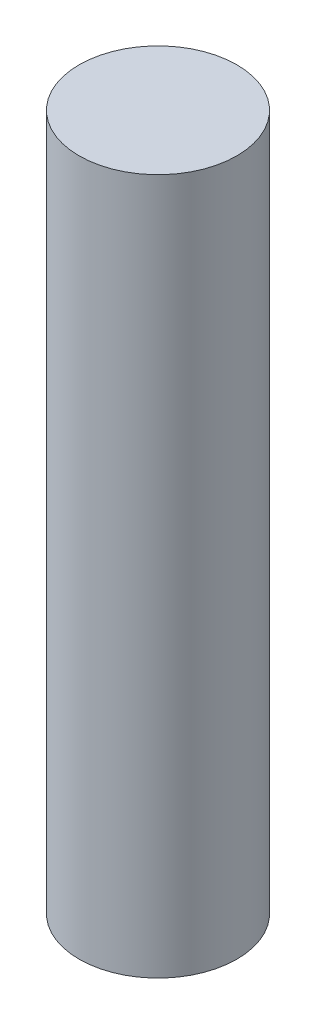
SolidWorks part; units mm, degrees
material "Alloy Steel"
ref_plane "Front Plane" through (0, 0, 0) normal (0, 0, 1) x (1, 0, 0)
ref_plane "Top Plane" through (0, 0, 0) normal (0, 1, 0) x (1, 0, 0)
ref_plane "Right Plane" through (0, 0, 0) normal (1, 0, 0) x (0, 0, -1)
sketch "Sketch1" plane through (0, 0, 0) normal (0, 1, 0) x (1, 0, 0)
  circle A0 centre (0, 0) radius 3.9688
  dimension "D1" = 7.9375
extrude "Boss-Extrude1" add sketch "Sketch1" along normal blind 35
